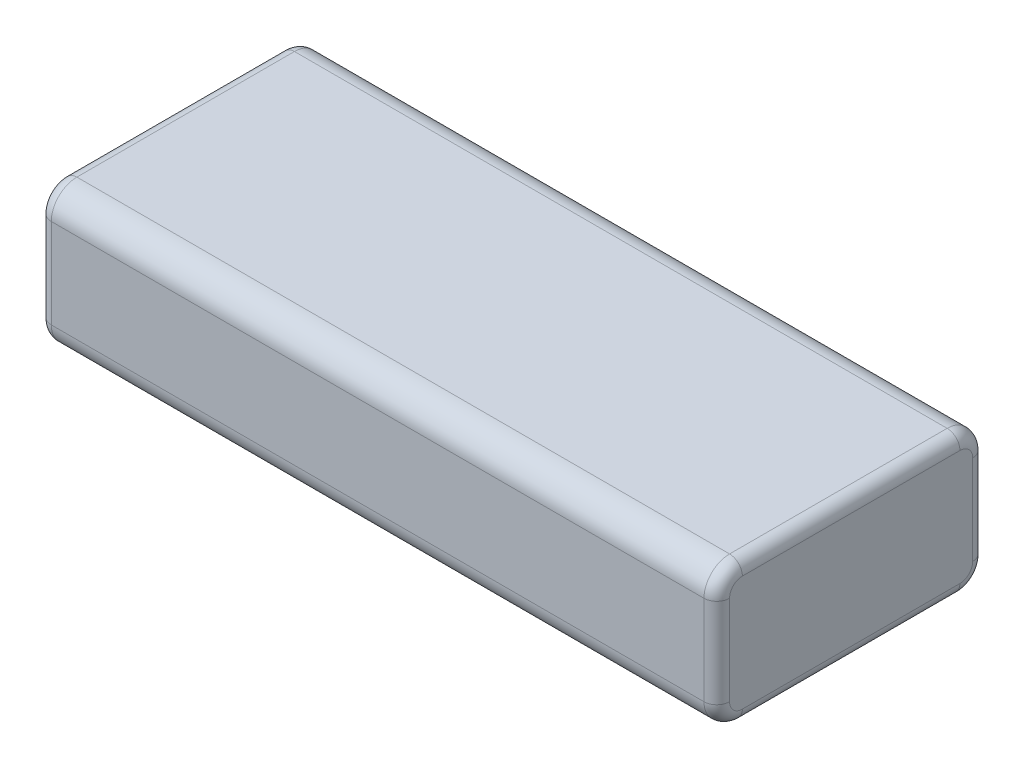
SolidWorks part; units mm, degrees
ref_plane "Front Plane" through (0, 0, 0) normal (0, 0, 1) x (1, 0, 0)
ref_plane "Top Plane" through (0, 0, 0) normal (0, 1, 0) x (1, 0, 0)
ref_plane "Right Plane" through (0, 0, 0) normal (1, 0, 0) x (0, 0, -1)
sketch "Sketch1" plane through (0, 0, 0) normal (0, 1, 0) x (1, 0, 0)
  line L1 (26.5, -10.5) -> (-26.5, -10.5)
  line L2 (26.5, -10.5) -> (26.5, 10.5)
  line L3 (26.5, 10.5) -> (-26.5, 10.5)
  line L4 (-26.5, -10.5) -> (-26.5, 10.5)
  line L5 (26.5, -10.5) -> (-26.5, 10.5) construction
  line L6 (26.5, 10.5) -> (-26.5, -10.5) construction
  point P0 (0, 0)
  dimension "D1" = 21
  dimension "D2" = 53
extrude "Boss-Extrude1" add sketch "Sketch1" along normal blind 11
fillet "Fillet1" radius 1 8 edges at (-26.5, 5.5, -10.5) (-26.5, 11, 0) (-26.5, 5.5, 10.5) (-26.5, 0, 0) (26.5, 5.5, 10.5) (26.5, 11, 0) (26.5, 5.5, -10.5) (26.5, 0, 0)
fillet "Fillet2" radius 2 12 edges at (-26.2071, 10.7071, -10.2071) (26.2071, 10.7071, -10.2071) (26.2071, 10.7071, 10.2071) (-26.2071, 10.7071, 10.2071) (26.2071, 0.2929, 10.2071) (-26.2071, 0.2929, 10.2071) (-26.2071, 0.2929, -10.2071) (26.2071, 0.2929, -10.2071) (0, 0, -10.5) (0, 0, 10.5) (0, 11, 10.5) (0, 11, -10.5)
